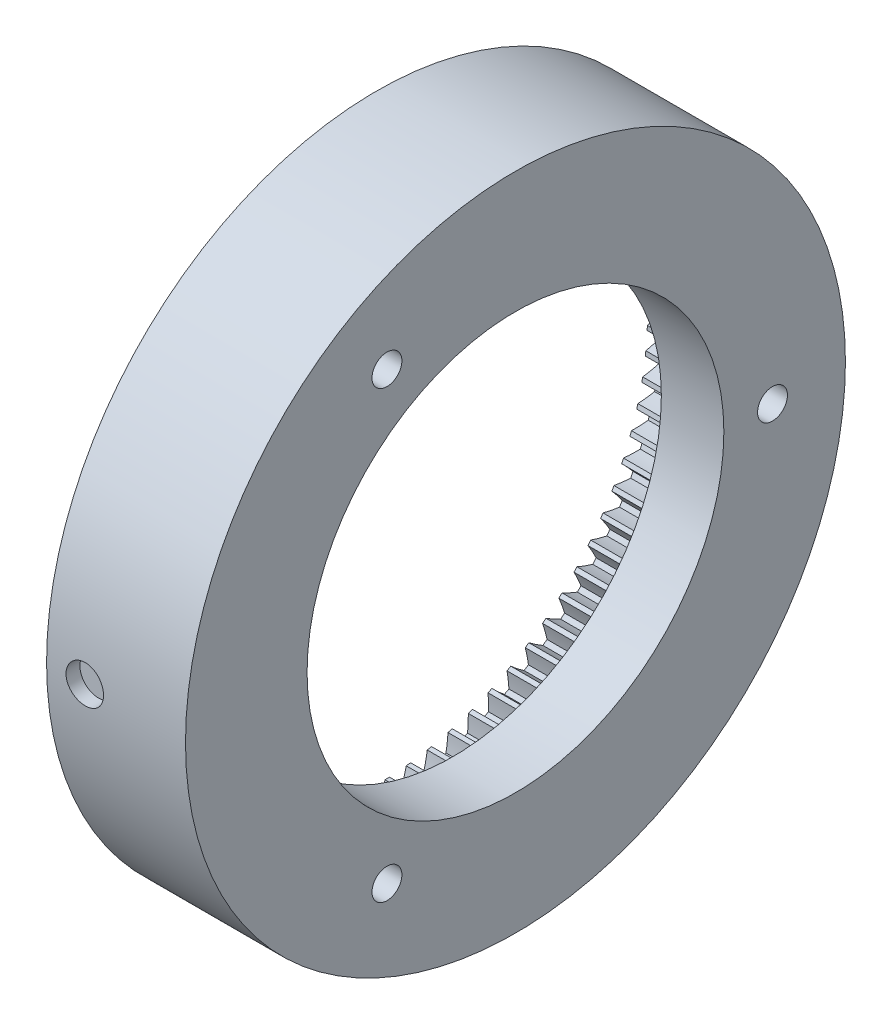
SolidWorks part; units mm, degrees
ref_plane "Plane1" through (0, 0, 0) normal (0, 0, 1) x (1, 0, 0)
ref_plane "Plane2" through (0, 0, 0) normal (0, 1, 0) x (1, 0, 0)
ref_plane "Plane3" through (0, 0, 0) normal (1, 0, 0) x (0, 0, -1)
other "Configuration Table"
sketch "HoldingSke" plane through (0, 0, 0) normal (0, 1, 0) x (1, 0, 0)
  line L0 (0, 0) -> (0.1736, -0.9848)
  line L1 (-15, 0) -> (100, 0) construction
  line L2 (0, 0) -> (-2.1039, 2.3779)
  line L3 (0, 0) -> (-11.863, 4.5341)
  line L4 (0, 0) -> (1.4996, 8.5048)
  line L5 (0, 0) -> (-23.7986, -8.8762)
  line L6 (0, 0) -> (-10.5278, -7.1032)
  line L7 (-2.1039, 2.3779) -> (3.3635, 27.1825)
  line L8 (-76.2, 3.3779) -> (-54.61, 3.3779)
  line L9 (-71.009, 38.7566) -> (-53.1078, 45.2721)
  line L10 (-76.2, 71.12) -> (104.1128, 71.12)
  line L11 (0, 0) -> (-10, 0)
  line L12 (-76.2, 101.6) -> (-76.162, 101.6)
  line L13 (24.9733, 27.94) -> (52.9518, 28.4284)
  line L14 (24.9733, 27.94) -> (24.9743, 27.94)
  line L15 (24.9733, 27.94) -> (100.4006, 29.5858)
  circle A0 centre (0, 0) radius 47.5
  circle A1 centre (0, 0) radius 12.7
  circle A2 centre (0, 0) radius 12.7
  dimension "Num_teeth" = 80
  dimension "Pitch_radius" = 180.3128
  dimension "Width" = 10
  dimension "Diameter" = 95
sketch "BasProSke" plane through (0, 0, 0) normal (0, 1, 0) x (1, 0, 0)
  line L0 (-10, 0) -> (60, 0) construction
  line L1 (0, 39) -> (0, 47.5)
  line L2 (0, 39) -> (10, 39)
  line L3 (10, 39) -> (10, 47.5)
  line L4 (10, 47.5) -> (0, 47.5)
  dimension "Thickness" = 10
  dimension "Diameter" = 95
revolve "Base-Revolve" add sketch "BasProSke" angle 360 about L0
sketch "TooCutSke" plane through (0, 0, 0) normal (1, 0, 0) x (0, 0, -1)
  line L3 (0.8803, 39.9903) -> (0.8803, 53.6633) construction
  line L4 (0, 0) -> (0, 59.563) construction
  line L5 (0, 0) -> (-2.6825, 68.2748) construction
  line L6 (-17.914, 33.1512) -> (36.4855, 35.2886) construction
  circle A0 centre (0, 0) radius 40 construction
  circle A1 centre (0, 0) radius 41.251 construction
  circle A2 centre (0, 0) radius 33.8289 construction
  circle A3 centre (0, 0) radius 38.9746 construction
  arc A4 (1.2253, 38.9553) -> (0.3732, 41.2493) centre (-17.914, 33.1512) ccw
  arc A5 (1.2253, 38.9553) -> (-1.2253, 38.9553) centre (0, 0) ccw
  arc A6 (0.3732, 41.2493) -> (-0.3732, 41.2493) centre (0, 0) ccw
  arc A7 (-0.3732, 41.2493) -> (-1.2253, 38.9553) centre (17.914, 33.1512) ccw
extrude "ToothCut" cut sketch "TooCutSke" along normal through all
fillet "Breaks" [suppressed] radius 0.1
fillet "RootFillets" [suppressed] radius 0.251
pattern_circular "TeethCuts" count 80 every 4.5 about axis through (-10, 0, 0) along (1, 0, 0) of "RootFillets", "Breaks", "ToothCut"
sketch "Sketch1" plane through (10, 0, 0) normal (1, 0, 0) x (0, 0, -1)
  circle A1 centre (0, 0) radius 47.5
  circle A2 centre (0, 0) radius 47.5
  arc A322 (2.8643, 41.1514) -> (1.8447, 38.9564) centre (20.4598, 31.6435) ccw
  arc A323 (3.6084, 41.0929) -> (2.8643, 41.1514) centre (0, 0) ccw
  arc A324 (4.2722, 38.7653) -> (3.6084, 41.0929) centre (-15.2577, 34.4545) ccw
  arc A325 (4.8955, 38.6915) -> (4.2722, 38.7653) centre (0, 0) ccw
  arc A326 (6.0842, 40.7998) -> (4.8955, 38.6915) centre (22.8794, 29.9407) ccw
  arc A327 (6.8214, 40.6831) -> (6.0842, 40.7998) centre (0, 0) ccw
  arc A328 (7.3005, 38.3106) -> (6.8214, 40.6831) centre (-12.5074, 35.5454) ccw
  arc A329 (7.9161, 38.1882) -> (7.3005, 38.3106) centre (0, 0) ccw
  arc A330 (9.2666, 40.1967) -> (7.9161, 38.1882) centre (25.158, 28.0533) ccw
  arc A331 (9.9923, 40.0225) -> (9.2666, 40.1967) centre (0, 0) ccw
  arc A332 (10.2838, 37.6197) -> (9.9923, 40.0225) centre (-9.68, 36.4172) ccw
  arc A333 (10.8879, 37.4494) -> (10.2838, 37.6197) centre (0, 0) ccw
  arc A334 (12.3918, 39.3458) -> (10.8879, 37.4494) centre (27.2815, 25.9929) ccw
  arc A335 (13.1017, 39.1151) -> (12.3918, 39.3458) centre (0, 0) ccw
  arc A336 (13.2037, 36.6969) -> (13.1017, 39.1151) centre (-6.7929, 37.0644) ccw
  arc A337 (13.7926, 36.4797) -> (13.2037, 36.6969) centre (0, 0) ccw
  arc A338 (15.4406, 38.2522) -> (13.7926, 36.4797) centre (29.2368, 23.7723) ccw
  arc A339 (16.1302, 37.9666) -> (15.4406, 38.2522) centre (0, 0) ccw
  arc A340 (16.0422, 35.5478) -> (16.1302, 37.9666) centre (-3.8639, 37.4831) ccw
  arc A341 (16.6122, 35.2851) -> (16.0422, 35.5478) centre (0, 0) ccw
  arc A342 (18.3943, 36.9228) -> (16.6122, 35.2851) centre (31.0118, 21.4052) ccw
  arc A343 (19.0593, 36.584) -> (18.3943, 36.9228) centre (0, 0) ccw
  arc A344 (18.7818, 34.1796) -> (19.0593, 36.584) centre (-0.9111, 37.6707) ccw
  arc A345 (19.3294, 33.8729) -> (18.7818, 34.1796) centre (0, 0) ccw
  arc A346 (21.2345, 35.3658) -> (19.3294, 33.8729) centre (32.5956, 18.906) ccw
  arc A347 (21.8709, 34.9758) -> (21.2345, 35.3658) centre (0, 0) ccw
  arc A348 (21.4056, 32.6006) -> (21.8709, 34.9758) centre (2.0473, 37.6261) ccw
  arc A349 (21.9275, 32.2519) -> (21.4056, 32.6006) centre (0, 0) ccw
  arc A350 (23.9438, 33.5908) -> (21.9275, 32.2519) centre (33.9785, 16.2903) ccw
  arc A351 (24.5477, 33.152) -> (23.9438, 33.5908) centre (0, 0) ccw
  arc A352 (23.8974, 30.8207) -> (24.5477, 33.152) centre (4.9931, 37.3494) ccw
  arc A353 (24.3903, 30.4321) -> (23.8974, 30.8207) centre (0, 0) ccw
  arc A354 (26.5055, 31.6086) -> (24.3903, 30.4321) centre (35.1519, 13.5742) ccw
  arc A355 (27.0731, 31.1239) -> (26.5055, 31.6086) centre (0, 0) ccw
  arc A356 (26.2419, 28.8507) -> (27.0731, 31.1239) centre (7.9081, 36.8426) ccw
  arc A357 (26.7028, 28.4246) -> (26.2419, 28.8507) centre (0, 0) ccw
  arc A358 (28.9038, 29.4316) -> (26.7028, 28.4246) centre (36.1085, 10.7743) ccw
  arc A359 (29.4316, 28.9038) -> (28.9038, 29.4316) centre (0, 0) ccw
  arc A360 (28.4246, 26.7028) -> (29.4316, 28.9038) centre (10.7743, 36.1085) ccw
  arc A361 (28.8507, 26.2419) -> (28.4246, 26.7028) centre (0, 0) ccw
  arc A362 (31.1239, 27.0731) -> (28.8507, 26.2419) centre (36.8426, 7.9081) ccw
  arc A363 (31.6086, 26.5055) -> (31.1239, 27.0731) centre (0, 0) ccw
  arc A364 (30.4321, 24.3903) -> (31.6086, 26.5055) centre (13.5742, 35.1519) ccw
  arc A365 (30.8207, 23.8974) -> (30.4321, 24.3903) centre (0, 0) ccw
  arc A366 (33.152, 24.5477) -> (30.8207, 23.8974) centre (37.3494, 4.9931) ccw
  arc A367 (33.5908, 23.9438) -> (33.152, 24.5477) centre (0, 0) ccw
  arc A368 (32.2519, 21.9275) -> (33.5908, 23.9438) centre (16.2903, 33.9785) ccw
  arc A369 (32.6006, 21.4056) -> (32.2519, 21.9275) centre (0, 0) ccw
  arc A370 (34.9758, 21.8709) -> (32.6006, 21.4056) centre (37.6261, 2.0473) ccw
  arc A371 (35.3658, 21.2345) -> (34.9758, 21.8709) centre (0, 0) ccw
  arc A372 (33.8729, 19.3294) -> (35.3658, 21.2345) centre (18.906, 32.5956) ccw
  arc A373 (34.1796, 18.7818) -> (33.8729, 19.3294) centre (0, 0) ccw
  arc A374 (36.584, 19.0593) -> (34.1796, 18.7818) centre (37.6707, -0.9111) ccw
  arc A375 (36.9228, 18.3943) -> (36.584, 19.0593) centre (0, 0) ccw
  arc A376 (35.2851, 16.6122) -> (36.9228, 18.3943) centre (21.4052, 31.0118) ccw
  arc A377 (35.5478, 16.0422) -> (35.2851, 16.6122) centre (0, 0) ccw
  arc A378 (37.9666, 16.1302) -> (35.5478, 16.0422) centre (37.4831, -3.8639) ccw
  arc A379 (38.2522, 15.4406) -> (37.9666, 16.1302) centre (0, 0) ccw
  arc A380 (36.4797, 13.7926) -> (38.2522, 15.4406) centre (23.7723, 29.2368) ccw
  arc A381 (36.6969, 13.2037) -> (36.4797, 13.7926) centre (0, 0) ccw
  arc A382 (39.1151, 13.1017) -> (36.6969, 13.2037) centre (37.0644, -6.7929) ccw
  arc A383 (39.3458, 12.3918) -> (39.1151, 13.1017) centre (0, 0) ccw
  arc A384 (37.4494, 10.8879) -> (39.3458, 12.3918) centre (25.9929, 27.2815) ccw
  arc A385 (37.6197, 10.2838) -> (37.4494, 10.8879) centre (0, 0) ccw
  arc A386 (40.0225, 9.9923) -> (37.6197, 10.2838) centre (36.4172, -9.68) ccw
  arc A387 (40.1967, 9.2666) -> (40.0225, 9.9923) centre (0, 0) ccw
  arc A388 (38.1882, 7.9161) -> (40.1967, 9.2666) centre (28.0533, 25.158) ccw
  arc A389 (38.3106, 7.3005) -> (38.1882, 7.9161) centre (0, 0) ccw
  arc A390 (40.6831, 6.8214) -> (38.3106, 7.3005) centre (35.5454, -12.5074) ccw
  arc A391 (40.7998, 6.0842) -> (40.6831, 6.8214) centre (0, 0) ccw
  arc A392 (38.6915, 4.8955) -> (40.7998, 6.0842) centre (29.9407, 22.8794) ccw
  arc A393 (38.7653, 4.2722) -> (38.6915, 4.8955) centre (0, 0) ccw
  arc A394 (41.0929, 3.6084) -> (38.7653, 4.2722) centre (34.4545, -15.2577) ccw
  arc A395 (41.1514, 2.8643) -> (41.0929, 3.6084) centre (0, 0) ccw
  arc A396 (38.9564, 1.8447) -> (41.1514, 2.8643) centre (31.6435, 20.4598) ccw
  arc A397 (38.981, 1.2175) -> (38.9564, 1.8447) centre (0, 0) ccw
  arc A398 (41.2493, 0.3732) -> (38.981, 1.2175) centre (33.1512, -17.914) ccw
  arc A399 (41.2493, -0.3732) -> (41.2493, 0.3732) centre (0, 0) ccw
  arc A400 (38.981, -1.2175) -> (41.2493, -0.3732) centre (33.1512, 17.914) ccw
  arc A401 (38.9564, -1.8447) -> (38.981, -1.2175) centre (0, 0) ccw
  arc A402 (41.1514, -2.8643) -> (38.9564, -1.8447) centre (31.6435, -20.4598) ccw
  arc A403 (41.0929, -3.6084) -> (41.1514, -2.8643) centre (0, 0) ccw
  arc A404 (38.7653, -4.2722) -> (41.0929, -3.6084) centre (34.4545, 15.2577) ccw
  arc A405 (38.6915, -4.8955) -> (38.7653, -4.2722) centre (0, 0) ccw
  arc A406 (40.7998, -6.0842) -> (38.6915, -4.8955) centre (29.9407, -22.8794) ccw
  arc A407 (40.6831, -6.8214) -> (40.7998, -6.0842) centre (0, 0) ccw
  arc A408 (38.3106, -7.3005) -> (40.6831, -6.8214) centre (35.5454, 12.5074) ccw
  arc A409 (38.1882, -7.9161) -> (38.3106, -7.3005) centre (0, 0) ccw
  arc A410 (40.1967, -9.2666) -> (38.1882, -7.9161) centre (28.0533, -25.158) ccw
  arc A411 (40.0225, -9.9923) -> (40.1967, -9.2666) centre (0, 0) ccw
  arc A412 (37.6197, -10.2838) -> (40.0225, -9.9923) centre (36.4172, 9.68) ccw
  arc A413 (37.4494, -10.8879) -> (37.6197, -10.2838) centre (0, 0) ccw
  arc A414 (39.3458, -12.3918) -> (37.4494, -10.8879) centre (25.9929, -27.2815) ccw
  arc A415 (39.1151, -13.1017) -> (39.3458, -12.3918) centre (0, 0) ccw
  arc A416 (36.6969, -13.2037) -> (39.1151, -13.1017) centre (37.0644, 6.7929) ccw
  arc A417 (36.4797, -13.7926) -> (36.6969, -13.2037) centre (0, 0) ccw
  arc A418 (38.2522, -15.4406) -> (36.4797, -13.7926) centre (23.7723, -29.2368) ccw
  arc A419 (37.9666, -16.1302) -> (38.2522, -15.4406) centre (0, 0) ccw
  arc A420 (35.5478, -16.0422) -> (37.9666, -16.1302) centre (37.4831, 3.8639) ccw
  arc A421 (35.2851, -16.6122) -> (35.5478, -16.0422) centre (0, 0) ccw
  arc A422 (36.9228, -18.3943) -> (35.2851, -16.6122) centre (21.4052, -31.0118) ccw
  arc A423 (36.584, -19.0593) -> (36.9228, -18.3943) centre (0, 0) ccw
  arc A424 (34.1796, -18.7818) -> (36.584, -19.0593) centre (37.6707, 0.9111) ccw
  arc A425 (33.8729, -19.3294) -> (34.1796, -18.7818) centre (0, 0) ccw
  arc A426 (35.3658, -21.2345) -> (33.8729, -19.3294) centre (18.906, -32.5956) ccw
  arc A427 (34.9758, -21.8709) -> (35.3658, -21.2345) centre (0, 0) ccw
  arc A428 (32.6006, -21.4056) -> (34.9758, -21.8709) centre (37.6261, -2.0473) ccw
  arc A429 (32.2519, -21.9275) -> (32.6006, -21.4056) centre (0, 0) ccw
  arc A430 (33.5908, -23.9438) -> (32.2519, -21.9275) centre (16.2903, -33.9785) ccw
  arc A431 (33.152, -24.5477) -> (33.5908, -23.9438) centre (0, 0) ccw
  arc A432 (30.8207, -23.8974) -> (33.152, -24.5477) centre (37.3494, -4.9931) ccw
  arc A433 (30.4321, -24.3903) -> (30.8207, -23.8974) centre (0, 0) ccw
  arc A434 (31.6086, -26.5055) -> (30.4321, -24.3903) centre (13.5742, -35.1519) ccw
  arc A435 (31.1239, -27.0731) -> (31.6086, -26.5055) centre (0, 0) ccw
  arc A436 (28.8507, -26.2419) -> (31.1239, -27.0731) centre (36.8426, -7.9081) ccw
  arc A437 (28.4246, -26.7028) -> (28.8507, -26.2419) centre (0, 0) ccw
  arc A438 (29.4316, -28.9038) -> (28.4246, -26.7028) centre (10.7743, -36.1085) ccw
  arc A439 (28.9038, -29.4316) -> (29.4316, -28.9038) centre (0, 0) ccw
  arc A440 (26.7028, -28.4246) -> (28.9038, -29.4316) centre (36.1085, -10.7743) ccw
  arc A441 (26.2419, -28.8507) -> (26.7028, -28.4246) centre (0, 0) ccw
  arc A442 (27.0731, -31.1239) -> (26.2419, -28.8507) centre (7.9081, -36.8426) ccw
  arc A443 (26.5055, -31.6086) -> (27.0731, -31.1239) centre (0, 0) ccw
  arc A444 (24.3903, -30.4321) -> (26.5055, -31.6086) centre (35.1519, -13.5742) ccw
  arc A445 (23.8974, -30.8207) -> (24.3903, -30.4321) centre (0, 0) ccw
  arc A446 (24.5477, -33.152) -> (23.8974, -30.8207) centre (4.9931, -37.3494) ccw
  arc A447 (23.9438, -33.5908) -> (24.5477, -33.152) centre (0, 0) ccw
  arc A448 (21.9275, -32.2519) -> (23.9438, -33.5908) centre (33.9785, -16.2903) ccw
  arc A449 (21.4056, -32.6006) -> (21.9275, -32.2519) centre (0, 0) ccw
  arc A450 (21.8709, -34.9758) -> (21.4056, -32.6006) centre (2.0473, -37.6261) ccw
  arc A451 (21.2345, -35.3658) -> (21.8709, -34.9758) centre (0, 0) ccw
  arc A452 (19.3294, -33.8729) -> (21.2345, -35.3658) centre (32.5956, -18.906) ccw
  arc A453 (18.7818, -34.1796) -> (19.3294, -33.8729) centre (0, 0) ccw
  arc A454 (19.0593, -36.584) -> (18.7818, -34.1796) centre (-0.9111, -37.6707) ccw
  arc A455 (18.3943, -36.9228) -> (19.0593, -36.584) centre (0, 0) ccw
  arc A456 (16.6122, -35.2851) -> (18.3943, -36.9228) centre (31.0118, -21.4052) ccw
  arc A457 (16.0422, -35.5478) -> (16.6122, -35.2851) centre (0, 0) ccw
  arc A458 (16.1302, -37.9666) -> (16.0422, -35.5478) centre (-3.8639, -37.4831) ccw
  arc A459 (15.4406, -38.2522) -> (16.1302, -37.9666) centre (0, 0) ccw
  arc A460 (13.7926, -36.4797) -> (15.4406, -38.2522) centre (29.2368, -23.7723) ccw
  arc A461 (13.2037, -36.6969) -> (13.7926, -36.4797) centre (0, 0) ccw
  arc A462 (13.1017, -39.1151) -> (13.2037, -36.6969) centre (-6.7929, -37.0644) ccw
  arc A463 (12.3918, -39.3458) -> (13.1017, -39.1151) centre (0, 0) ccw
  arc A464 (10.8879, -37.4494) -> (12.3918, -39.3458) centre (27.2815, -25.9929) ccw
  arc A465 (10.2838, -37.6197) -> (10.8879, -37.4494) centre (0, 0) ccw
  arc A466 (9.9923, -40.0225) -> (10.2838, -37.6197) centre (-9.68, -36.4172) ccw
  arc A467 (9.2666, -40.1967) -> (9.9923, -40.0225) centre (0, 0) ccw
  arc A468 (7.9161, -38.1882) -> (9.2666, -40.1967) centre (25.158, -28.0533) ccw
  arc A469 (7.3005, -38.3106) -> (7.9161, -38.1882) centre (0, 0) ccw
  arc A470 (6.8214, -40.6831) -> (7.3005, -38.3106) centre (-12.5074, -35.5454) ccw
  arc A471 (6.0842, -40.7998) -> (6.8214, -40.6831) centre (0, 0) ccw
  arc A472 (4.8955, -38.6915) -> (6.0842, -40.7998) centre (22.8794, -29.9407) ccw
  arc A473 (4.2722, -38.7653) -> (4.8955, -38.6915) centre (0, 0) ccw
  arc A474 (3.6084, -41.0929) -> (4.2722, -38.7653) centre (-15.2577, -34.4545) ccw
  arc A475 (2.8643, -41.1514) -> (3.6084, -41.0929) centre (0, 0) ccw
  arc A476 (1.8447, -38.9564) -> (2.8643, -41.1514) centre (20.4598, -31.6435) ccw
  arc A477 (1.2175, -38.981) -> (1.8447, -38.9564) centre (0, 0) ccw
  arc A478 (0.3732, -41.2493) -> (1.2175, -38.981) centre (-17.914, -33.1512) ccw
  arc A479 (-0.3732, -41.2493) -> (0.3732, -41.2493) centre (0, 0) ccw
  arc A480 (-1.2175, -38.981) -> (-0.3732, -41.2493) centre (17.914, -33.1512) ccw
  arc A481 (-1.8447, -38.9564) -> (-1.2175, -38.981) centre (0, 0) ccw
  arc A482 (-2.8643, -41.1514) -> (-1.8447, -38.9564) centre (-20.4598, -31.6435) ccw
  arc A483 (-3.6084, -41.0929) -> (-2.8643, -41.1514) centre (0, 0) ccw
  arc A484 (-4.2722, -38.7653) -> (-3.6084, -41.0929) centre (15.2577, -34.4545) ccw
  arc A485 (-4.8955, -38.6915) -> (-4.2722, -38.7653) centre (0, 0) ccw
  arc A486 (-6.0842, -40.7998) -> (-4.8955, -38.6915) centre (-22.8794, -29.9407) ccw
  arc A487 (-6.8214, -40.6831) -> (-6.0842, -40.7998) centre (0, 0) ccw
  arc A488 (-7.3005, -38.3106) -> (-6.8214, -40.6831) centre (12.5074, -35.5454) ccw
  arc A489 (-7.9161, -38.1882) -> (-7.3005, -38.3106) centre (0, 0) ccw
  arc A490 (-9.2666, -40.1967) -> (-7.9161, -38.1882) centre (-25.158, -28.0533) ccw
  arc A491 (-9.9923, -40.0225) -> (-9.2666, -40.1967) centre (0, 0) ccw
  arc A492 (-10.2838, -37.6197) -> (-9.9923, -40.0225) centre (9.68, -36.4172) ccw
  arc A493 (-10.8879, -37.4494) -> (-10.2838, -37.6197) centre (0, 0) ccw
  arc A494 (-12.3918, -39.3458) -> (-10.8879, -37.4494) centre (-27.2815, -25.9929) ccw
  arc A495 (-13.1017, -39.1151) -> (-12.3918, -39.3458) centre (0, 0) ccw
  arc A496 (-13.2037, -36.6969) -> (-13.1017, -39.1151) centre (6.7929, -37.0644) ccw
  arc A497 (-13.7926, -36.4797) -> (-13.2037, -36.6969) centre (0, 0) ccw
  arc A498 (-15.4406, -38.2522) -> (-13.7926, -36.4797) centre (-29.2368, -23.7723) ccw
  arc A499 (-16.1302, -37.9666) -> (-15.4406, -38.2522) centre (0, 0) ccw
  arc A500 (-16.0422, -35.5478) -> (-16.1302, -37.9666) centre (3.8639, -37.4831) ccw
  arc A501 (-16.6122, -35.2851) -> (-16.0422, -35.5478) centre (0, 0) ccw
  arc A502 (-18.3943, -36.9228) -> (-16.6122, -35.2851) centre (-31.0118, -21.4052) ccw
  arc A503 (-19.0593, -36.584) -> (-18.3943, -36.9228) centre (0, 0) ccw
  arc A504 (-18.7818, -34.1796) -> (-19.0593, -36.584) centre (0.9111, -37.6707) ccw
  arc A505 (-19.3294, -33.8729) -> (-18.7818, -34.1796) centre (0, 0) ccw
  arc A506 (-21.2345, -35.3658) -> (-19.3294, -33.8729) centre (-32.5956, -18.906) ccw
  arc A507 (-21.8709, -34.9758) -> (-21.2345, -35.3658) centre (0, 0) ccw
  arc A508 (-21.4056, -32.6006) -> (-21.8709, -34.9758) centre (-2.0473, -37.6261) ccw
  arc A509 (-21.9275, -32.2519) -> (-21.4056, -32.6006) centre (0, 0) ccw
  arc A510 (-23.9438, -33.5908) -> (-21.9275, -32.2519) centre (-33.9785, -16.2903) ccw
  arc A511 (-24.5477, -33.152) -> (-23.9438, -33.5908) centre (0, 0) ccw
  arc A512 (-23.8974, -30.8207) -> (-24.5477, -33.152) centre (-4.9931, -37.3494) ccw
  arc A513 (-24.3903, -30.4321) -> (-23.8974, -30.8207) centre (0, 0) ccw
  arc A514 (-26.5055, -31.6086) -> (-24.3903, -30.4321) centre (-35.1519, -13.5742) ccw
  arc A515 (-27.0731, -31.1239) -> (-26.5055, -31.6086) centre (0, 0) ccw
  arc A516 (-26.2419, -28.8507) -> (-27.0731, -31.1239) centre (-7.9081, -36.8426) ccw
  arc A517 (-26.7028, -28.4246) -> (-26.2419, -28.8507) centre (0, 0) ccw
  arc A518 (-28.9038, -29.4316) -> (-26.7028, -28.4246) centre (-36.1085, -10.7743) ccw
  arc A519 (-29.4316, -28.9038) -> (-28.9038, -29.4316) centre (0, 0) ccw
  arc A520 (-28.4246, -26.7028) -> (-29.4316, -28.9038) centre (-10.7743, -36.1085) ccw
  arc A521 (-28.8507, -26.2419) -> (-28.4246, -26.7028) centre (0, 0) ccw
  arc A522 (-31.1239, -27.0731) -> (-28.8507, -26.2419) centre (-36.8426, -7.9081) ccw
  arc A523 (-31.6086, -26.5055) -> (-31.1239, -27.0731) centre (0, 0) ccw
  arc A524 (-30.4321, -24.3903) -> (-31.6086, -26.5055) centre (-13.5742, -35.1519) ccw
  arc A525 (-30.8207, -23.8974) -> (-30.4321, -24.3903) centre (0, 0) ccw
  arc A526 (-33.152, -24.5477) -> (-30.8207, -23.8974) centre (-37.3494, -4.9931) ccw
  arc A527 (-33.5908, -23.9438) -> (-33.152, -24.5477) centre (0, 0) ccw
  arc A528 (-32.2519, -21.9275) -> (-33.5908, -23.9438) centre (-16.2903, -33.9785) ccw
  arc A529 (-32.6006, -21.4056) -> (-32.2519, -21.9275) centre (0, 0) ccw
  arc A530 (-34.9758, -21.8709) -> (-32.6006, -21.4056) centre (-37.6261, -2.0473) ccw
  arc A531 (-35.3658, -21.2345) -> (-34.9758, -21.8709) centre (0, 0) ccw
  arc A532 (-33.8729, -19.3294) -> (-35.3658, -21.2345) centre (-18.906, -32.5956) ccw
  arc A533 (-34.1796, -18.7818) -> (-33.8729, -19.3294) centre (0, 0) ccw
  arc A534 (-36.584, -19.0593) -> (-34.1796, -18.7818) centre (-37.6707, 0.9111) ccw
  arc A535 (-36.9228, -18.3943) -> (-36.584, -19.0593) centre (0, 0) ccw
  arc A536 (-35.2851, -16.6122) -> (-36.9228, -18.3943) centre (-21.4052, -31.0118) ccw
  arc A537 (-35.5478, -16.0422) -> (-35.2851, -16.6122) centre (0, 0) ccw
  arc A538 (-37.9666, -16.1302) -> (-35.5478, -16.0422) centre (-37.4831, 3.8639) ccw
  arc A539 (-38.2522, -15.4406) -> (-37.9666, -16.1302) centre (0, 0) ccw
  arc A540 (-36.4797, -13.7926) -> (-38.2522, -15.4406) centre (-23.7723, -29.2368) ccw
  arc A541 (-36.6969, -13.2037) -> (-36.4797, -13.7926) centre (0, 0) ccw
  arc A542 (-39.1151, -13.1017) -> (-36.6969, -13.2037) centre (-37.0644, 6.7929) ccw
  arc A543 (-39.3458, -12.3918) -> (-39.1151, -13.1017) centre (0, 0) ccw
  arc A544 (-37.4494, -10.8879) -> (-39.3458, -12.3918) centre (-25.9929, -27.2815) ccw
  arc A545 (-37.6197, -10.2838) -> (-37.4494, -10.8879) centre (0, 0) ccw
  arc A546 (-40.0225, -9.9923) -> (-37.6197, -10.2838) centre (-36.4172, 9.68) ccw
  arc A547 (-40.1967, -9.2666) -> (-40.0225, -9.9923) centre (0, 0) ccw
  arc A548 (-38.1882, -7.9161) -> (-40.1967, -9.2666) centre (-28.0533, -25.158) ccw
  arc A549 (-38.3106, -7.3005) -> (-38.1882, -7.9161) centre (0, 0) ccw
  arc A550 (-40.6831, -6.8214) -> (-38.3106, -7.3005) centre (-35.5454, 12.5074) ccw
  arc A551 (-40.7998, -6.0842) -> (-40.6831, -6.8214) centre (0, 0) ccw
  arc A552 (-38.6915, -4.8955) -> (-40.7998, -6.0842) centre (-29.9407, -22.8794) ccw
  arc A553 (-38.7653, -4.2722) -> (-38.6915, -4.8955) centre (0, 0) ccw
  arc A554 (-41.0929, -3.6084) -> (-38.7653, -4.2722) centre (-34.4545, 15.2577) ccw
  arc A555 (-41.1514, -2.8643) -> (-41.0929, -3.6084) centre (0, 0) ccw
  arc A556 (-38.9564, -1.8447) -> (-41.1514, -2.8643) centre (-31.6435, -20.4598) ccw
  arc A557 (-38.981, -1.2175) -> (-38.9564, -1.8447) centre (0, 0) ccw
  arc A558 (-41.2493, -0.3732) -> (-38.981, -1.2175) centre (-33.1512, 17.914) ccw
  arc A559 (-41.2493, 0.3732) -> (-41.2493, -0.3732) centre (0, 0) ccw
  arc A560 (-38.981, 1.2175) -> (-41.2493, 0.3732) centre (-33.1512, -17.914) ccw
  arc A561 (-38.9564, 1.8447) -> (-38.981, 1.2175) centre (0, 0) ccw
  arc A562 (-41.1514, 2.8643) -> (-38.9564, 1.8447) centre (-31.6435, 20.4598) ccw
  arc A563 (-41.0929, 3.6084) -> (-41.1514, 2.8643) centre (0, 0) ccw
  arc A564 (-38.7653, 4.2722) -> (-41.0929, 3.6084) centre (-34.4545, -15.2577) ccw
  arc A565 (-38.6915, 4.8955) -> (-38.7653, 4.2722) centre (0, 0) ccw
  arc A566 (-40.7998, 6.0842) -> (-38.6915, 4.8955) centre (-29.9407, 22.8794) ccw
  arc A567 (-40.6831, 6.8214) -> (-40.7998, 6.0842) centre (0, 0) ccw
  arc A568 (-38.3106, 7.3005) -> (-40.6831, 6.8214) centre (-35.5454, -12.5074) ccw
  arc A569 (-38.1882, 7.9161) -> (-38.3106, 7.3005) centre (0, 0) ccw
  arc A570 (-40.1967, 9.2666) -> (-38.1882, 7.9161) centre (-28.0533, 25.158) ccw
  arc A571 (-40.0225, 9.9923) -> (-40.1967, 9.2666) centre (0, 0) ccw
  arc A572 (-37.6197, 10.2838) -> (-40.0225, 9.9923) centre (-36.4172, -9.68) ccw
  arc A573 (-37.4494, 10.8879) -> (-37.6197, 10.2838) centre (0, 0) ccw
  arc A574 (-39.3458, 12.3918) -> (-37.4494, 10.8879) centre (-25.9929, 27.2815) ccw
  arc A575 (-39.1151, 13.1017) -> (-39.3458, 12.3918) centre (0, 0) ccw
  arc A576 (-36.6969, 13.2037) -> (-39.1151, 13.1017) centre (-37.0644, -6.7929) ccw
  arc A577 (-36.4797, 13.7926) -> (-36.6969, 13.2037) centre (0, 0) ccw
  arc A578 (-38.2522, 15.4406) -> (-36.4797, 13.7926) centre (-23.7723, 29.2368) ccw
  arc A579 (-37.9666, 16.1302) -> (-38.2522, 15.4406) centre (0, 0) ccw
  arc A580 (-35.5478, 16.0422) -> (-37.9666, 16.1302) centre (-37.4831, -3.8639) ccw
  arc A581 (-35.2851, 16.6122) -> (-35.5478, 16.0422) centre (0, 0) ccw
  arc A582 (-36.9228, 18.3943) -> (-35.2851, 16.6122) centre (-21.4052, 31.0118) ccw
  arc A583 (-36.584, 19.0593) -> (-36.9228, 18.3943) centre (0, 0) ccw
  arc A584 (-34.1796, 18.7818) -> (-36.584, 19.0593) centre (-37.6707, -0.9111) ccw
  arc A585 (-33.8729, 19.3294) -> (-34.1796, 18.7818) centre (0, 0) ccw
  arc A586 (-35.3658, 21.2345) -> (-33.8729, 19.3294) centre (-18.906, 32.5956) ccw
  arc A587 (-34.9758, 21.8709) -> (-35.3658, 21.2345) centre (0, 0) ccw
  arc A588 (-32.6006, 21.4056) -> (-34.9758, 21.8709) centre (-37.6261, 2.0473) ccw
  arc A589 (-32.2519, 21.9275) -> (-32.6006, 21.4056) centre (0, 0) ccw
  arc A590 (-33.5908, 23.9438) -> (-32.2519, 21.9275) centre (-16.2903, 33.9785) ccw
  arc A591 (-33.152, 24.5477) -> (-33.5908, 23.9438) centre (0, 0) ccw
  arc A592 (-30.8207, 23.8974) -> (-33.152, 24.5477) centre (-37.3494, 4.9931) ccw
  arc A593 (-30.4321, 24.3903) -> (-30.8207, 23.8974) centre (0, 0) ccw
  arc A594 (-31.6086, 26.5055) -> (-30.4321, 24.3903) centre (-13.5742, 35.1519) ccw
  arc A595 (-31.1239, 27.0731) -> (-31.6086, 26.5055) centre (0, 0) ccw
  arc A596 (-28.8507, 26.2419) -> (-31.1239, 27.0731) centre (-36.8426, 7.9081) ccw
  arc A597 (-28.4246, 26.7028) -> (-28.8507, 26.2419) centre (0, 0) ccw
  arc A598 (-29.4316, 28.9038) -> (-28.4246, 26.7028) centre (-10.7743, 36.1085) ccw
  arc A599 (-28.9038, 29.4316) -> (-29.4316, 28.9038) centre (0, 0) ccw
  arc A600 (-26.7028, 28.4246) -> (-28.9038, 29.4316) centre (-36.1085, 10.7743) ccw
  arc A601 (-26.2419, 28.8507) -> (-26.7028, 28.4246) centre (0, 0) ccw
  arc A602 (-27.0731, 31.1239) -> (-26.2419, 28.8507) centre (-7.9081, 36.8426) ccw
  arc A603 (-26.5055, 31.6086) -> (-27.0731, 31.1239) centre (0, 0) ccw
  arc A604 (-24.3903, 30.4321) -> (-26.5055, 31.6086) centre (-35.1519, 13.5742) ccw
  arc A605 (-23.8974, 30.8207) -> (-24.3903, 30.4321) centre (0, 0) ccw
  arc A606 (-24.5477, 33.152) -> (-23.8974, 30.8207) centre (-4.9931, 37.3494) ccw
  arc A607 (-23.9438, 33.5908) -> (-24.5477, 33.152) centre (0, 0) ccw
  arc A608 (-21.9275, 32.2519) -> (-23.9438, 33.5908) centre (-33.9785, 16.2903) ccw
  arc A609 (-21.4056, 32.6006) -> (-21.9275, 32.2519) centre (0, 0) ccw
  arc A610 (-21.8709, 34.9758) -> (-21.4056, 32.6006) centre (-2.0473, 37.6261) ccw
  arc A611 (-21.2345, 35.3658) -> (-21.8709, 34.9758) centre (0, 0) ccw
  arc A612 (-19.3294, 33.8729) -> (-21.2345, 35.3658) centre (-32.5956, 18.906) ccw
  arc A613 (-18.7818, 34.1796) -> (-19.3294, 33.8729) centre (0, 0) ccw
  arc A614 (-19.0593, 36.584) -> (-18.7818, 34.1796) centre (0.9111, 37.6707) ccw
  arc A615 (-18.3943, 36.9228) -> (-19.0593, 36.584) centre (0, 0) ccw
  arc A616 (-16.6122, 35.2851) -> (-18.3943, 36.9228) centre (-31.0118, 21.4052) ccw
  arc A617 (-16.0422, 35.5478) -> (-16.6122, 35.2851) centre (0, 0) ccw
  arc A618 (-16.1302, 37.9666) -> (-16.0422, 35.5478) centre (3.8639, 37.4831) ccw
  arc A619 (-15.4406, 38.2522) -> (-16.1302, 37.9666) centre (0, 0) ccw
  arc A620 (-13.7926, 36.4797) -> (-15.4406, 38.2522) centre (-29.2368, 23.7723) ccw
  arc A621 (-13.2037, 36.6969) -> (-13.7926, 36.4797) centre (0, 0) ccw
  arc A622 (-13.1017, 39.1151) -> (-13.2037, 36.6969) centre (6.7929, 37.0644) ccw
  arc A623 (-12.3918, 39.3458) -> (-13.1017, 39.1151) centre (0, 0) ccw
  arc A624 (-10.8879, 37.4494) -> (-12.3918, 39.3458) centre (-27.2815, 25.9929) ccw
  arc A625 (-10.2838, 37.6197) -> (-10.8879, 37.4494) centre (0, 0) ccw
  arc A626 (-9.9923, 40.0225) -> (-10.2838, 37.6197) centre (9.68, 36.4172) ccw
  arc A627 (-9.2666, 40.1967) -> (-9.9923, 40.0225) centre (0, 0) ccw
  arc A628 (-7.9161, 38.1882) -> (-9.2666, 40.1967) centre (-25.158, 28.0533) ccw
  arc A629 (-7.3005, 38.3106) -> (-7.9161, 38.1882) centre (0, 0) ccw
  arc A630 (-6.8214, 40.6831) -> (-7.3005, 38.3106) centre (12.5074, 35.5454) ccw
  arc A631 (-6.0842, 40.7998) -> (-6.8214, 40.6831) centre (0, 0) ccw
  arc A632 (-4.8955, 38.6915) -> (-6.0842, 40.7998) centre (-22.8794, 29.9407) ccw
  arc A633 (-4.2722, 38.7653) -> (-4.8955, 38.6915) centre (0, 0) ccw
  arc A634 (-3.6084, 41.0929) -> (-4.2722, 38.7653) centre (15.2577, 34.4545) ccw
  arc A635 (-2.8643, 41.1514) -> (-3.6084, 41.0929) centre (0, 0) ccw
  arc A636 (-1.8447, 38.9564) -> (-2.8643, 41.1514) centre (-20.4598, 31.6435) ccw
  arc A637 (-1.2175, 38.981) -> (-1.8447, 38.9564) centre (0, 0) ccw
  arc A638 (-0.3732, 41.2493) -> (-1.2175, 38.981) centre (17.914, 33.1512) ccw
  arc A639 (0.3732, 41.2493) -> (-0.3732, 41.2493) centre (0, 0) ccw
  arc A640 (1.2175, 38.981) -> (0.3732, 41.2493) centre (-17.914, 33.1512) ccw
  arc A641 (1.8447, 38.9564) -> (1.2175, 38.981) centre (0, 0) ccw
  arc A642 (2.8643, 41.1514) -> (1.8447, 38.9564) centre (20.4598, 31.6435) ccw
  arc A643 (3.6084, 41.0929) -> (2.8643, 41.1514) centre (0, 0) ccw
  arc A644 (4.2722, 38.7653) -> (3.6084, 41.0929) centre (-15.2577, 34.4545) ccw
  arc A645 (4.8955, 38.6915) -> (4.2722, 38.7653) centre (0, 0) ccw
  arc A646 (6.0842, 40.7998) -> (4.8955, 38.6915) centre (22.8794, 29.9407) ccw
  arc A647 (6.8214, 40.6831) -> (6.0842, 40.7998) centre (0, 0) ccw
  arc A648 (7.3005, 38.3106) -> (6.8214, 40.6831) centre (-12.5074, 35.5454) ccw
  arc A649 (7.9161, 38.1882) -> (7.3005, 38.3106) centre (0, 0) ccw
  arc A650 (9.2666, 40.1967) -> (7.9161, 38.1882) centre (25.158, 28.0533) ccw
  arc A651 (9.9923, 40.0225) -> (9.2666, 40.1967) centre (0, 0) ccw
  arc A652 (10.2838, 37.6197) -> (9.9923, 40.0225) centre (-9.68, 36.4172) ccw
  arc A653 (10.8879, 37.4494) -> (10.2838, 37.6197) centre (0, 0) ccw
  arc A654 (12.3918, 39.3458) -> (10.8879, 37.4494) centre (27.2815, 25.9929) ccw
  arc A655 (13.1017, 39.1151) -> (12.3918, 39.3458) centre (0, 0) ccw
  arc A656 (13.2037, 36.6969) -> (13.1017, 39.1151) centre (-6.7929, 37.0644) ccw
  arc A657 (13.7926, 36.4797) -> (13.2037, 36.6969) centre (0, 0) ccw
  arc A658 (15.4406, 38.2522) -> (13.7926, 36.4797) centre (29.2368, 23.7723) ccw
  arc A659 (16.1302, 37.9666) -> (15.4406, 38.2522) centre (0, 0) ccw
  arc A660 (16.0422, 35.5478) -> (16.1302, 37.9666) centre (-3.8639, 37.4831) ccw
  arc A661 (16.6122, 35.2851) -> (16.0422, 35.5478) centre (0, 0) ccw
  arc A662 (18.3943, 36.9228) -> (16.6122, 35.2851) centre (31.0118, 21.4052) ccw
  arc A663 (19.0593, 36.584) -> (18.3943, 36.9228) centre (0, 0) ccw
  arc A664 (18.7818, 34.1796) -> (19.0593, 36.584) centre (-0.9111, 37.6707) ccw
  arc A665 (19.3294, 33.8729) -> (18.7818, 34.1796) centre (0, 0) ccw
  arc A666 (21.2345, 35.3658) -> (19.3294, 33.8729) centre (32.5956, 18.906) ccw
  arc A667 (21.8709, 34.9758) -> (21.2345, 35.3658) centre (0, 0) ccw
  arc A668 (21.4056, 32.6006) -> (21.8709, 34.9758) centre (2.0473, 37.6261) ccw
  arc A669 (21.9275, 32.2519) -> (21.4056, 32.6006) centre (0, 0) ccw
  arc A670 (23.9438, 33.5908) -> (21.9275, 32.2519) centre (33.9785, 16.2903) ccw
  arc A671 (24.5477, 33.152) -> (23.9438, 33.5908) centre (0, 0) ccw
  arc A672 (23.8974, 30.8207) -> (24.5477, 33.152) centre (4.9931, 37.3494) ccw
  arc A673 (24.3903, 30.4321) -> (23.8974, 30.8207) centre (0, 0) ccw
  arc A674 (26.5055, 31.6086) -> (24.3903, 30.4321) centre (35.1519, 13.5742) ccw
  arc A675 (27.0731, 31.1239) -> (26.5055, 31.6086) centre (0, 0) ccw
  arc A676 (26.2419, 28.8507) -> (27.0731, 31.1239) centre (7.9081, 36.8426) ccw
  arc A677 (26.7028, 28.4246) -> (26.2419, 28.8507) centre (0, 0) ccw
  arc A678 (28.9038, 29.4316) -> (26.7028, 28.4246) centre (36.1085, 10.7743) ccw
  arc A679 (29.4316, 28.9038) -> (28.9038, 29.4316) centre (0, 0) ccw
  arc A680 (28.4246, 26.7028) -> (29.4316, 28.9038) centre (10.7743, 36.1085) ccw
  arc A681 (28.8507, 26.2419) -> (28.4246, 26.7028) centre (0, 0) ccw
  arc A682 (31.1239, 27.0731) -> (28.8507, 26.2419) centre (36.8426, 7.9081) ccw
  arc A683 (31.6086, 26.5055) -> (31.1239, 27.0731) centre (0, 0) ccw
  arc A684 (30.4321, 24.3903) -> (31.6086, 26.5055) centre (13.5742, 35.1519) ccw
  arc A685 (30.8207, 23.8974) -> (30.4321, 24.3903) centre (0, 0) ccw
  arc A686 (33.152, 24.5477) -> (30.8207, 23.8974) centre (37.3494, 4.9931) ccw
  arc A687 (33.5908, 23.9438) -> (33.152, 24.5477) centre (0, 0) ccw
  arc A688 (32.2519, 21.9275) -> (33.5908, 23.9438) centre (16.2903, 33.9785) ccw
  arc A689 (32.6006, 21.4056) -> (32.2519, 21.9275) centre (0, 0) ccw
  arc A690 (34.9758, 21.8709) -> (32.6006, 21.4056) centre (37.6261, 2.0473) ccw
  arc A691 (35.3658, 21.2345) -> (34.9758, 21.8709) centre (0, 0) ccw
  arc A692 (33.8729, 19.3294) -> (35.3658, 21.2345) centre (18.906, 32.5956) ccw
  arc A693 (34.1796, 18.7818) -> (33.8729, 19.3294) centre (0, 0) ccw
  arc A694 (36.584, 19.0593) -> (34.1796, 18.7818) centre (37.6707, -0.9111) ccw
  arc A695 (36.9228, 18.3943) -> (36.584, 19.0593) centre (0, 0) ccw
  arc A696 (35.2851, 16.6122) -> (36.9228, 18.3943) centre (21.4052, 31.0118) ccw
  arc A697 (35.5478, 16.0422) -> (35.2851, 16.6122) centre (0, 0) ccw
  arc A698 (37.9666, 16.1302) -> (35.5478, 16.0422) centre (37.4831, -3.8639) ccw
  arc A699 (38.2522, 15.4406) -> (37.9666, 16.1302) centre (0, 0) ccw
  arc A700 (36.4797, 13.7926) -> (38.2522, 15.4406) centre (23.7723, 29.2368) ccw
  arc A701 (36.6969, 13.2037) -> (36.4797, 13.7926) centre (0, 0) ccw
  arc A702 (39.1151, 13.1017) -> (36.6969, 13.2037) centre (37.0644, -6.7929) ccw
  arc A703 (39.3458, 12.3918) -> (39.1151, 13.1017) centre (0, 0) ccw
  arc A704 (37.4494, 10.8879) -> (39.3458, 12.3918) centre (25.9929, 27.2815) ccw
  arc A705 (37.6197, 10.2838) -> (37.4494, 10.8879) centre (0, 0) ccw
  arc A706 (40.0225, 9.9923) -> (37.6197, 10.2838) centre (36.4172, -9.68) ccw
  arc A707 (40.1967, 9.2666) -> (40.0225, 9.9923) centre (0, 0) ccw
  arc A708 (38.1882, 7.9161) -> (40.1967, 9.2666) centre (28.0533, 25.158) ccw
  arc A709 (38.3106, 7.3005) -> (38.1882, 7.9161) centre (0, 0) ccw
  arc A710 (40.6831, 6.8214) -> (38.3106, 7.3005) centre (35.5454, -12.5074) ccw
  arc A711 (40.7998, 6.0842) -> (40.6831, 6.8214) centre (0, 0) ccw
  arc A712 (38.6915, 4.8955) -> (40.7998, 6.0842) centre (29.9407, 22.8794) ccw
  arc A713 (38.7653, 4.2722) -> (38.6915, 4.8955) centre (0, 0) ccw
  arc A714 (41.0929, 3.6084) -> (38.7653, 4.2722) centre (34.4545, -15.2577) ccw
  arc A715 (41.1514, 2.8643) -> (41.0929, 3.6084) centre (0, 0) ccw
  arc A716 (38.9564, 1.8447) -> (41.1514, 2.8643) centre (31.6435, 20.4598) ccw
  arc A717 (38.981, 1.2175) -> (38.9564, 1.8447) centre (0, 0) ccw
  arc A718 (41.2493, 0.3732) -> (38.981, 1.2175) centre (33.1512, -17.914) ccw
  arc A719 (41.2493, -0.3732) -> (41.2493, 0.3732) centre (0, 0) ccw
  arc A720 (38.981, -1.2175) -> (41.2493, -0.3732) centre (33.1512, 17.914) ccw
  arc A721 (38.9564, -1.8447) -> (38.981, -1.2175) centre (0, 0) ccw
  arc A722 (41.1514, -2.8643) -> (38.9564, -1.8447) centre (31.6435, -20.4598) ccw
  arc A723 (41.0929, -3.6084) -> (41.1514, -2.8643) centre (0, 0) ccw
  arc A724 (38.7653, -4.2722) -> (41.0929, -3.6084) centre (34.4545, 15.2577) ccw
  arc A725 (38.6915, -4.8955) -> (38.7653, -4.2722) centre (0, 0) ccw
  arc A726 (40.7998, -6.0842) -> (38.6915, -4.8955) centre (29.9407, -22.8794) ccw
  arc A727 (40.6831, -6.8214) -> (40.7998, -6.0842) centre (0, 0) ccw
  arc A728 (38.3106, -7.3005) -> (40.6831, -6.8214) centre (35.5454, 12.5074) ccw
  arc A729 (38.1882, -7.9161) -> (38.3106, -7.3005) centre (0, 0) ccw
  arc A730 (40.1967, -9.2666) -> (38.1882, -7.9161) centre (28.0533, -25.158) ccw
  arc A731 (40.0225, -9.9923) -> (40.1967, -9.2666) centre (0, 0) ccw
  arc A732 (37.6197, -10.2838) -> (40.0225, -9.9923) centre (36.4172, 9.68) ccw
  arc A733 (37.4494, -10.8879) -> (37.6197, -10.2838) centre (0, 0) ccw
  arc A734 (39.3458, -12.3918) -> (37.4494, -10.8879) centre (25.9929, -27.2815) ccw
  arc A735 (39.1151, -13.1017) -> (39.3458, -12.3918) centre (0, 0) ccw
  arc A736 (36.6969, -13.2037) -> (39.1151, -13.1017) centre (37.0644, 6.7929) ccw
  arc A737 (36.4797, -13.7926) -> (36.6969, -13.2037) centre (0, 0) ccw
  arc A738 (38.2522, -15.4406) -> (36.4797, -13.7926) centre (23.7723, -29.2368) ccw
  arc A739 (37.9666, -16.1302) -> (38.2522, -15.4406) centre (0, 0) ccw
  arc A740 (35.5478, -16.0422) -> (37.9666, -16.1302) centre (37.4831, 3.8639) ccw
  arc A741 (35.2851, -16.6122) -> (35.5478, -16.0422) centre (0, 0) ccw
  arc A742 (36.9228, -18.3943) -> (35.2851, -16.6122) centre (21.4052, -31.0118) ccw
  arc A743 (36.584, -19.0593) -> (36.9228, -18.3943) centre (0, 0) ccw
  arc A744 (34.1796, -18.7818) -> (36.584, -19.0593) centre (37.6707, 0.9111) ccw
  arc A745 (33.8729, -19.3294) -> (34.1796, -18.7818) centre (0, 0) ccw
  arc A746 (35.3658, -21.2345) -> (33.8729, -19.3294) centre (18.906, -32.5956) ccw
  arc A747 (34.9758, -21.8709) -> (35.3658, -21.2345) centre (0, 0) ccw
  arc A748 (32.6006, -21.4056) -> (34.9758, -21.8709) centre (37.6261, -2.0473) ccw
  arc A749 (32.2519, -21.9275) -> (32.6006, -21.4056) centre (0, 0) ccw
  arc A750 (33.5908, -23.9438) -> (32.2519, -21.9275) centre (16.2903, -33.9785) ccw
  arc A751 (33.152, -24.5477) -> (33.5908, -23.9438) centre (0, 0) ccw
  arc A752 (30.8207, -23.8974) -> (33.152, -24.5477) centre (37.3494, -4.9931) ccw
  arc A753 (30.4321, -24.3903) -> (30.8207, -23.8974) centre (0, 0) ccw
  arc A754 (31.6086, -26.5055) -> (30.4321, -24.3903) centre (13.5742, -35.1519) ccw
  arc A755 (31.1239, -27.0731) -> (31.6086, -26.5055) centre (0, 0) ccw
  arc A756 (28.8507, -26.2419) -> (31.1239, -27.0731) centre (36.8426, -7.9081) ccw
  arc A757 (28.4246, -26.7028) -> (28.8507, -26.2419) centre (0, 0) ccw
  arc A758 (29.4316, -28.9038) -> (28.4246, -26.7028) centre (10.7743, -36.1085) ccw
  arc A759 (28.9038, -29.4316) -> (29.4316, -28.9038) centre (0, 0) ccw
  arc A760 (26.7028, -28.4246) -> (28.9038, -29.4316) centre (36.1085, -10.7743) ccw
  arc A761 (26.2419, -28.8507) -> (26.7028, -28.4246) centre (0, 0) ccw
  arc A762 (27.0731, -31.1239) -> (26.2419, -28.8507) centre (7.9081, -36.8426) ccw
  arc A763 (26.5055, -31.6086) -> (27.0731, -31.1239) centre (0, 0) ccw
  arc A764 (24.3903, -30.4321) -> (26.5055, -31.6086) centre (35.1519, -13.5742) ccw
  arc A765 (23.8974, -30.8207) -> (24.3903, -30.4321) centre (0, 0) ccw
  arc A766 (24.5477, -33.152) -> (23.8974, -30.8207) centre (4.9931, -37.3494) ccw
  arc A767 (23.9438, -33.5908) -> (24.5477, -33.152) centre (0, 0) ccw
  arc A768 (21.9275, -32.2519) -> (23.9438, -33.5908) centre (33.9785, -16.2903) ccw
  arc A769 (21.4056, -32.6006) -> (21.9275, -32.2519) centre (0, 0) ccw
  arc A770 (21.8709, -34.9758) -> (21.4056, -32.6006) centre (2.0473, -37.6261) ccw
  arc A771 (21.2345, -35.3658) -> (21.8709, -34.9758) centre (0, 0) ccw
  arc A772 (19.3294, -33.8729) -> (21.2345, -35.3658) centre (32.5956, -18.906) ccw
  arc A773 (18.7818, -34.1796) -> (19.3294, -33.8729) centre (0, 0) ccw
  arc A774 (19.0593, -36.584) -> (18.7818, -34.1796) centre (-0.9111, -37.6707) ccw
  arc A775 (18.3943, -36.9228) -> (19.0593, -36.584) centre (0, 0) ccw
  arc A776 (16.6122, -35.2851) -> (18.3943, -36.9228) centre (31.0118, -21.4052) ccw
  arc A777 (16.0422, -35.5478) -> (16.6122, -35.2851) centre (0, 0) ccw
  arc A778 (16.1302, -37.9666) -> (16.0422, -35.5478) centre (-3.8639, -37.4831) ccw
  arc A779 (15.4406, -38.2522) -> (16.1302, -37.9666) centre (0, 0) ccw
  arc A780 (13.7926, -36.4797) -> (15.4406, -38.2522) centre (29.2368, -23.7723) ccw
  arc A781 (13.2037, -36.6969) -> (13.7926, -36.4797) centre (0, 0) ccw
  arc A782 (13.1017, -39.1151) -> (13.2037, -36.6969) centre (-6.7929, -37.0644) ccw
  arc A783 (12.3918, -39.3458) -> (13.1017, -39.1151) centre (0, 0) ccw
  arc A784 (10.8879, -37.4494) -> (12.3918, -39.3458) centre (27.2815, -25.9929) ccw
  arc A785 (10.2838, -37.6197) -> (10.8879, -37.4494) centre (0, 0) ccw
  arc A786 (9.9923, -40.0225) -> (10.2838, -37.6197) centre (-9.68, -36.4172) ccw
  arc A787 (9.2666, -40.1967) -> (9.9923, -40.0225) centre (0, 0) ccw
  arc A788 (7.9161, -38.1882) -> (9.2666, -40.1967) centre (25.158, -28.0533) ccw
  arc A789 (7.3005, -38.3106) -> (7.9161, -38.1882) centre (0, 0) ccw
  arc A790 (6.8214, -40.6831) -> (7.3005, -38.3106) centre (-12.5074, -35.5454) ccw
  arc A791 (6.0842, -40.7998) -> (6.8214, -40.6831) centre (0, 0) ccw
  arc A792 (4.8955, -38.6915) -> (6.0842, -40.7998) centre (22.8794, -29.9407) ccw
  arc A793 (4.2722, -38.7653) -> (4.8955, -38.6915) centre (0, 0) ccw
  arc A794 (3.6084, -41.0929) -> (4.2722, -38.7653) centre (-15.2577, -34.4545) ccw
  arc A795 (2.8643, -41.1514) -> (3.6084, -41.0929) centre (0, 0) ccw
  arc A796 (1.8447, -38.9564) -> (2.8643, -41.1514) centre (20.4598, -31.6435) ccw
  arc A797 (1.2175, -38.981) -> (1.8447, -38.9564) centre (0, 0) ccw
  arc A798 (0.3732, -41.2493) -> (1.2175, -38.981) centre (-17.914, -33.1512) ccw
  arc A799 (-0.3732, -41.2493) -> (0.3732, -41.2493) centre (0, 0) ccw
  arc A800 (-1.2175, -38.981) -> (-0.3732, -41.2493) centre (17.914, -33.1512) ccw
  arc A801 (-1.8447, -38.9564) -> (-1.2175, -38.981) centre (0, 0) ccw
  arc A802 (-2.8643, -41.1514) -> (-1.8447, -38.9564) centre (-20.4598, -31.6435) ccw
  arc A803 (-3.6084, -41.0929) -> (-2.8643, -41.1514) centre (0, 0) ccw
  arc A804 (-4.2722, -38.7653) -> (-3.6084, -41.0929) centre (15.2577, -34.4545) ccw
  arc A805 (-4.8955, -38.6915) -> (-4.2722, -38.7653) centre (0, 0) ccw
  arc A806 (-6.0842, -40.7998) -> (-4.8955, -38.6915) centre (-22.8794, -29.9407) ccw
  arc A807 (-6.8214, -40.6831) -> (-6.0842, -40.7998) centre (0, 0) ccw
  arc A808 (-7.3005, -38.3106) -> (-6.8214, -40.6831) centre (12.5074, -35.5454) ccw
  arc A809 (-7.9161, -38.1882) -> (-7.3005, -38.3106) centre (0, 0) ccw
  arc A810 (-9.2666, -40.1967) -> (-7.9161, -38.1882) centre (-25.158, -28.0533) ccw
  arc A811 (-9.9923, -40.0225) -> (-9.2666, -40.1967) centre (0, 0) ccw
  arc A812 (-10.2838, -37.6197) -> (-9.9923, -40.0225) centre (9.68, -36.4172) ccw
  arc A813 (-10.8879, -37.4494) -> (-10.2838, -37.6197) centre (0, 0) ccw
  arc A814 (-12.3918, -39.3458) -> (-10.8879, -37.4494) centre (-27.2815, -25.9929) ccw
  arc A815 (-13.1017, -39.1151) -> (-12.3918, -39.3458) centre (0, 0) ccw
  arc A816 (-13.2037, -36.6969) -> (-13.1017, -39.1151) centre (6.7929, -37.0644) ccw
  arc A817 (-13.7926, -36.4797) -> (-13.2037, -36.6969) centre (0, 0) ccw
  arc A818 (-15.4406, -38.2522) -> (-13.7926, -36.4797) centre (-29.2368, -23.7723) ccw
  arc A819 (-16.1302, -37.9666) -> (-15.4406, -38.2522) centre (0, 0) ccw
  arc A820 (-16.0422, -35.5478) -> (-16.1302, -37.9666) centre (3.8639, -37.4831) ccw
  arc A821 (-16.6122, -35.2851) -> (-16.0422, -35.5478) centre (0, 0) ccw
  arc A822 (-18.3943, -36.9228) -> (-16.6122, -35.2851) centre (-31.0118, -21.4052) ccw
  arc A823 (-19.0593, -36.584) -> (-18.3943, -36.9228) centre (0, 0) ccw
  arc A824 (-18.7818, -34.1796) -> (-19.0593, -36.584) centre (0.9111, -37.6707) ccw
  arc A825 (-19.3294, -33.8729) -> (-18.7818, -34.1796) centre (0, 0) ccw
  arc A826 (-21.2345, -35.3658) -> (-19.3294, -33.8729) centre (-32.5956, -18.906) ccw
  arc A827 (-21.8709, -34.9758) -> (-21.2345, -35.3658) centre (0, 0) ccw
  arc A828 (-21.4056, -32.6006) -> (-21.8709, -34.9758) centre (-2.0473, -37.6261) ccw
  arc A829 (-21.9275, -32.2519) -> (-21.4056, -32.6006) centre (0, 0) ccw
  arc A830 (-23.9438, -33.5908) -> (-21.9275, -32.2519) centre (-33.9785, -16.2903) ccw
  arc A831 (-24.5477, -33.152) -> (-23.9438, -33.5908) centre (0, 0) ccw
  arc A832 (-23.8974, -30.8207) -> (-24.5477, -33.152) centre (-4.9931, -37.3494) ccw
  arc A833 (-24.3903, -30.4321) -> (-23.8974, -30.8207) centre (0, 0) ccw
  arc A834 (-26.5055, -31.6086) -> (-24.3903, -30.4321) centre (-35.1519, -13.5742) ccw
  arc A835 (-27.0731, -31.1239) -> (-26.5055, -31.6086) centre (0, 0) ccw
  arc A836 (-26.2419, -28.8507) -> (-27.0731, -31.1239) centre (-7.9081, -36.8426) ccw
  arc A837 (-26.7028, -28.4246) -> (-26.2419, -28.8507) centre (0, 0) ccw
  arc A838 (-28.9038, -29.4316) -> (-26.7028, -28.4246) centre (-36.1085, -10.7743) ccw
  arc A839 (-29.4316, -28.9038) -> (-28.9038, -29.4316) centre (0, 0) ccw
  arc A840 (-28.4246, -26.7028) -> (-29.4316, -28.9038) centre (-10.7743, -36.1085) ccw
  arc A841 (-28.8507, -26.2419) -> (-28.4246, -26.7028) centre (0, 0) ccw
  arc A842 (-31.1239, -27.0731) -> (-28.8507, -26.2419) centre (-36.8426, -7.9081) ccw
  arc A843 (-31.6086, -26.5055) -> (-31.1239, -27.0731) centre (0, 0) ccw
  arc A844 (-30.4321, -24.3903) -> (-31.6086, -26.5055) centre (-13.5742, -35.1519) ccw
  arc A845 (-30.8207, -23.8974) -> (-30.4321, -24.3903) centre (0, 0) ccw
  arc A846 (-33.152, -24.5477) -> (-30.8207, -23.8974) centre (-37.3494, -4.9931) ccw
  arc A847 (-33.5908, -23.9438) -> (-33.152, -24.5477) centre (0, 0) ccw
  arc A848 (-32.2519, -21.9275) -> (-33.5908, -23.9438) centre (-16.2903, -33.9785) ccw
  arc A849 (-32.6006, -21.4056) -> (-32.2519, -21.9275) centre (0, 0) ccw
  arc A850 (-34.9758, -21.8709) -> (-32.6006, -21.4056) centre (-37.6261, -2.0473) ccw
  arc A851 (-35.3658, -21.2345) -> (-34.9758, -21.8709) centre (0, 0) ccw
  arc A852 (-33.8729, -19.3294) -> (-35.3658, -21.2345) centre (-18.906, -32.5956) ccw
  arc A853 (-34.1796, -18.7818) -> (-33.8729, -19.3294) centre (0, 0) ccw
  arc A854 (-36.584, -19.0593) -> (-34.1796, -18.7818) centre (-37.6707, 0.9111) ccw
  arc A855 (-36.9228, -18.3943) -> (-36.584, -19.0593) centre (0, 0) ccw
  arc A856 (-35.2851, -16.6122) -> (-36.9228, -18.3943) centre (-21.4052, -31.0118) ccw
  arc A857 (-35.5478, -16.0422) -> (-35.2851, -16.6122) centre (0, 0) ccw
  arc A858 (-37.9666, -16.1302) -> (-35.5478, -16.0422) centre (-37.4831, 3.8639) ccw
  arc A859 (-38.2522, -15.4406) -> (-37.9666, -16.1302) centre (0, 0) ccw
  arc A860 (-36.4797, -13.7926) -> (-38.2522, -15.4406) centre (-23.7723, -29.2368) ccw
  arc A861 (-36.6969, -13.2037) -> (-36.4797, -13.7926) centre (0, 0) ccw
  arc A862 (-39.1151, -13.1017) -> (-36.6969, -13.2037) centre (-37.0644, 6.7929) ccw
  arc A863 (-39.3458, -12.3918) -> (-39.1151, -13.1017) centre (0, 0) ccw
  arc A864 (-37.4494, -10.8879) -> (-39.3458, -12.3918) centre (-25.9929, -27.2815) ccw
  arc A865 (-37.6197, -10.2838) -> (-37.4494, -10.8879) centre (0, 0) ccw
  arc A866 (-40.0225, -9.9923) -> (-37.6197, -10.2838) centre (-36.4172, 9.68) ccw
  arc A867 (-40.1967, -9.2666) -> (-40.0225, -9.9923) centre (0, 0) ccw
  arc A868 (-38.1882, -7.9161) -> (-40.1967, -9.2666) centre (-28.0533, -25.158) ccw
  arc A869 (-38.3106, -7.3005) -> (-38.1882, -7.9161) centre (0, 0) ccw
  arc A870 (-40.6831, -6.8214) -> (-38.3106, -7.3005) centre (-35.5454, 12.5074) ccw
  arc A871 (-40.7998, -6.0842) -> (-40.6831, -6.8214) centre (0, 0) ccw
  arc A872 (-38.6915, -4.8955) -> (-40.7998, -6.0842) centre (-29.9407, -22.8794) ccw
  arc A873 (-38.7653, -4.2722) -> (-38.6915, -4.8955) centre (0, 0) ccw
  arc A874 (-41.0929, -3.6084) -> (-38.7653, -4.2722) centre (-34.4545, 15.2577) ccw
  arc A875 (-41.1514, -2.8643) -> (-41.0929, -3.6084) centre (0, 0) ccw
  arc A876 (-38.9564, -1.8447) -> (-41.1514, -2.8643) centre (-31.6435, -20.4598) ccw
  arc A877 (-38.981, -1.2175) -> (-38.9564, -1.8447) centre (0, 0) ccw
  arc A878 (-41.2493, -0.3732) -> (-38.981, -1.2175) centre (-33.1512, 17.914) ccw
  arc A879 (-41.2493, 0.3732) -> (-41.2493, -0.3732) centre (0, 0) ccw
  arc A880 (-38.981, 1.2175) -> (-41.2493, 0.3732) centre (-33.1512, -17.914) ccw
  arc A881 (-38.9564, 1.8447) -> (-38.981, 1.2175) centre (0, 0) ccw
  arc A882 (-41.1514, 2.8643) -> (-38.9564, 1.8447) centre (-31.6435, 20.4598) ccw
  arc A883 (-41.0929, 3.6084) -> (-41.1514, 2.8643) centre (0, 0) ccw
  arc A884 (-38.7653, 4.2722) -> (-41.0929, 3.6084) centre (-34.4545, -15.2577) ccw
  arc A885 (-38.6915, 4.8955) -> (-38.7653, 4.2722) centre (0, 0) ccw
  arc A886 (-40.7998, 6.0842) -> (-38.6915, 4.8955) centre (-29.9407, 22.8794) ccw
  arc A887 (-40.6831, 6.8214) -> (-40.7998, 6.0842) centre (0, 0) ccw
  arc A888 (-38.3106, 7.3005) -> (-40.6831, 6.8214) centre (-35.5454, -12.5074) ccw
  arc A889 (-38.1882, 7.9161) -> (-38.3106, 7.3005) centre (0, 0) ccw
  arc A890 (-40.1967, 9.2666) -> (-38.1882, 7.9161) centre (-28.0533, 25.158) ccw
  arc A891 (-40.0225, 9.9923) -> (-40.1967, 9.2666) centre (0, 0) ccw
  arc A892 (-37.6197, 10.2838) -> (-40.0225, 9.9923) centre (-36.4172, -9.68) ccw
  arc A893 (-37.4494, 10.8879) -> (-37.6197, 10.2838) centre (0, 0) ccw
  arc A894 (-39.3458, 12.3918) -> (-37.4494, 10.8879) centre (-25.9929, 27.2815) ccw
  arc A895 (-39.1151, 13.1017) -> (-39.3458, 12.3918) centre (0, 0) ccw
  arc A896 (-36.6969, 13.2037) -> (-39.1151, 13.1017) centre (-37.0644, -6.7929) ccw
  arc A897 (-36.4797, 13.7926) -> (-36.6969, 13.2037) centre (0, 0) ccw
  arc A898 (-38.2522, 15.4406) -> (-36.4797, 13.7926) centre (-23.7723, 29.2368) ccw
  arc A899 (-37.9666, 16.1302) -> (-38.2522, 15.4406) centre (0, 0) ccw
  arc A900 (-35.5478, 16.0422) -> (-37.9666, 16.1302) centre (-37.4831, -3.8639) ccw
  arc A901 (-35.2851, 16.6122) -> (-35.5478, 16.0422) centre (0, 0) ccw
  arc A902 (-36.9228, 18.3943) -> (-35.2851, 16.6122) centre (-21.4052, 31.0118) ccw
  arc A903 (-36.584, 19.0593) -> (-36.9228, 18.3943) centre (0, 0) ccw
  arc A904 (-34.1796, 18.7818) -> (-36.584, 19.0593) centre (-37.6707, -0.9111) ccw
  arc A905 (-33.8729, 19.3294) -> (-34.1796, 18.7818) centre (0, 0) ccw
  arc A906 (-35.3658, 21.2345) -> (-33.8729, 19.3294) centre (-18.906, 32.5956) ccw
  arc A907 (-34.9758, 21.8709) -> (-35.3658, 21.2345) centre (0, 0) ccw
  arc A908 (-32.6006, 21.4056) -> (-34.9758, 21.8709) centre (-37.6261, 2.0473) ccw
  arc A909 (-32.2519, 21.9275) -> (-32.6006, 21.4056) centre (0, 0) ccw
  arc A910 (-33.5908, 23.9438) -> (-32.2519, 21.9275) centre (-16.2903, 33.9785) ccw
  arc A911 (-33.152, 24.5477) -> (-33.5908, 23.9438) centre (0, 0) ccw
  arc A912 (-30.8207, 23.8974) -> (-33.152, 24.5477) centre (-37.3494, 4.9931) ccw
  arc A913 (-30.4321, 24.3903) -> (-30.8207, 23.8974) centre (0, 0) ccw
  arc A914 (-31.6086, 26.5055) -> (-30.4321, 24.3903) centre (-13.5742, 35.1519) ccw
  arc A915 (-31.1239, 27.0731) -> (-31.6086, 26.5055) centre (0, 0) ccw
  arc A916 (-28.8507, 26.2419) -> (-31.1239, 27.0731) centre (-36.8426, 7.9081) ccw
  arc A917 (-28.4246, 26.7028) -> (-28.8507, 26.2419) centre (0, 0) ccw
  arc A918 (-29.4316, 28.9038) -> (-28.4246, 26.7028) centre (-10.7743, 36.1085) ccw
  arc A919 (-28.9038, 29.4316) -> (-29.4316, 28.9038) centre (0, 0) ccw
  arc A920 (-26.7028, 28.4246) -> (-28.9038, 29.4316) centre (-36.1085, 10.7743) ccw
  arc A921 (-26.2419, 28.8507) -> (-26.7028, 28.4246) centre (0, 0) ccw
  arc A922 (-27.0731, 31.1239) -> (-26.2419, 28.8507) centre (-7.9081, 36.8426) ccw
  arc A923 (-26.5055, 31.6086) -> (-27.0731, 31.1239) centre (0, 0) ccw
  arc A924 (-24.3903, 30.4321) -> (-26.5055, 31.6086) centre (-35.1519, 13.5742) ccw
  arc A925 (-23.8974, 30.8207) -> (-24.3903, 30.4321) centre (0, 0) ccw
  arc A926 (-24.5477, 33.152) -> (-23.8974, 30.8207) centre (-4.9931, 37.3494) ccw
  arc A927 (-23.9438, 33.5908) -> (-24.5477, 33.152) centre (0, 0) ccw
  arc A928 (-21.9275, 32.2519) -> (-23.9438, 33.5908) centre (-33.9785, 16.2903) ccw
  arc A929 (-21.4056, 32.6006) -> (-21.9275, 32.2519) centre (0, 0) ccw
  arc A930 (-21.8709, 34.9758) -> (-21.4056, 32.6006) centre (-2.0473, 37.6261) ccw
  arc A931 (-21.2345, 35.3658) -> (-21.8709, 34.9758) centre (0, 0) ccw
  arc A932 (-19.3294, 33.8729) -> (-21.2345, 35.3658) centre (-32.5956, 18.906) ccw
  arc A933 (-18.7818, 34.1796) -> (-19.3294, 33.8729) centre (0, 0) ccw
  arc A934 (-19.0593, 36.584) -> (-18.7818, 34.1796) centre (0.9111, 37.6707) ccw
  arc A935 (-18.3943, 36.9228) -> (-19.0593, 36.584) centre (0, 0) ccw
  arc A936 (-16.6122, 35.2851) -> (-18.3943, 36.9228) centre (-31.0118, 21.4052) ccw
  arc A937 (-16.0422, 35.5478) -> (-16.6122, 35.2851) centre (0, 0) ccw
  arc A938 (-16.1302, 37.9666) -> (-16.0422, 35.5478) centre (3.8639, 37.4831) ccw
  arc A939 (-15.4406, 38.2522) -> (-16.1302, 37.9666) centre (0, 0) ccw
  arc A940 (-13.7926, 36.4797) -> (-15.4406, 38.2522) centre (-29.2368, 23.7723) ccw
  arc A941 (-13.2037, 36.6969) -> (-13.7926, 36.4797) centre (0, 0) ccw
  arc A942 (-13.1017, 39.1151) -> (-13.2037, 36.6969) centre (6.7929, 37.0644) ccw
  arc A943 (-12.3918, 39.3458) -> (-13.1017, 39.1151) centre (0, 0) ccw
  arc A944 (-10.8879, 37.4494) -> (-12.3918, 39.3458) centre (-27.2815, 25.9929) ccw
  arc A945 (-10.2838, 37.6197) -> (-10.8879, 37.4494) centre (0, 0) ccw
  arc A946 (-9.9923, 40.0225) -> (-10.2838, 37.6197) centre (9.68, 36.4172) ccw
  arc A947 (-9.2666, 40.1967) -> (-9.9923, 40.0225) centre (0, 0) ccw
  arc A948 (-7.9161, 38.1882) -> (-9.2666, 40.1967) centre (-25.158, 28.0533) ccw
  arc A949 (-7.3005, 38.3106) -> (-7.9161, 38.1882) centre (0, 0) ccw
  arc A950 (-6.8214, 40.6831) -> (-7.3005, 38.3106) centre (12.5074, 35.5454) ccw
  arc A951 (-6.0842, 40.7998) -> (-6.8214, 40.6831) centre (0, 0) ccw
  arc A952 (-4.8955, 38.6915) -> (-6.0842, 40.7998) centre (-22.8794, 29.9407) ccw
  arc A953 (-4.2722, 38.7653) -> (-4.8955, 38.6915) centre (0, 0) ccw
  arc A954 (-3.6084, 41.0929) -> (-4.2722, 38.7653) centre (15.2577, 34.4545) ccw
  arc A955 (-2.8643, 41.1514) -> (-3.6084, 41.0929) centre (0, 0) ccw
  arc A956 (-1.8447, 38.9564) -> (-2.8643, 41.1514) centre (-20.4598, 31.6435) ccw
  arc A957 (-1.2175, 38.981) -> (-1.8447, 38.9564) centre (0, 0) ccw
  arc A958 (-0.3732, 41.2493) -> (-1.2175, 38.981) centre (17.914, 33.1512) ccw
  arc A959 (0.3732, 41.2493) -> (-0.3732, 41.2493) centre (0, 0) ccw
  arc A960 (1.2175, 38.981) -> (0.3732, 41.2493) centre (-17.914, 33.1512) ccw
  arc A961 (1.8447, 38.9564) -> (1.2175, 38.981) centre (0, 0) ccw
  dimension "D1" = 0
  dimension "D2" = 0
extrude "Boss-Extrude1" add sketch "Sketch1" along normal blind 1
sketch "Sketch3" plane through (11, 0, 0) normal (1, 0, 0) x (0, 0, -1)
  circle A0 centre (0, 0) radius 47.5 construction
  circle A1 centre (0, 0) radius 47.5
extrude "Boss-Extrude3" add sketch "Sketch3" along normal blind 9
sketch "Sketch4" plane through (20, 0, 0) normal (1, 0, 0) x (0, 0, -1)
  line L0 (0, 0) -> (37, 0) construction
  circle A0 centre (37, 0) radius 2.15
  circle A1 centre (37, 0) radius 11 construction
  circle A2 centre (0, 0) radius 48 construction
  circle A3 centre (-18.5, -32.0429) radius 2.15
  circle A4 centre (0, 0) radius 48 construction
  circle A5 centre (-18.5, 32.0429) radius 2.15
  circle A6 centre (0, 0) radius 48 construction
  circle A8 centre (0, 0) radius 30
  point P15 (0, 0)
  dimension "D1" = 4.3
  dimension "D2" = 96
  dimension "D3" = 22
  dimension "D5" = 60
  dimension "D4" = 3
extrude "Cut-Extrude1" cut sketch "Sketch4" against normal blind 7 contours A5 | A3 | A0 region at (20, 0, -37) region at (20, -32.0429, 18.5) region at (20, 32.0429, 18.5)
extrude "Cut-Extrude2" cut sketch "Sketch4<3>" against normal through all contours A8
sketch "Sketch4<3>" plane through (20, 0, 0) normal (1, 0, 0) x (0, 0, -1) same geometry as "Sketch4"
ref_plane "Plane4" through (0, 0, 47.5) normal (0, 0, 1) x (1, 0, 0)
sketch "Sketch7" plane through (0, 0, 47.5) normal (0, 0, 1) x (1, 0, 0)
  line L0 (0, 47.5) -> (0, -47.5) construction
  line L1 (11, 30) -> (11, -30) construction
  line L2 (0, 47.5) -> (0, -47.5) construction
  line L3 (11, 30) -> (11, -30) construction
  line L4 (11, 0) -> (0, 0) construction
  circle A0 centre (5.5, 0) radius 2.7
  dimension "D1" = 5.4
extrude "Cut-Extrude4" cut sketch "Sketch7" against normal blind 2
equation "' \"Module@HoldingSke\" = 6.35"
equation "' \"Num_teeth@HoldingSke\" = 24"
equation "' \"Ap@HoldingSke\" =  14.5"
equation "' \"Ap@HoldingSke\" = 14.5"
equation "' \"Width@HoldingSke\" = 12"
equation "' \"Diameter@HoldingSke\" = 8 * 25.4"
equation "' \"Show_teeth@HoldingSke\" = 100"
equation "' \"Backlash@HoldingSke\" = 0.009 * 25.4"
equation "' \"Addendum_fac@HoldingSke\" = 1.0"
equation "' \"Dedendum_fac@HoldingSke\" = 1.25"
equation "' \"Dedendum_add@HoldingSke\" = 0.00005 * 25.4"
equation "' \"Clearance_fac@HoldingSke\" = 0.25"
equation "\"Pitch@HoldingSke\" = 1 / \"Module@HoldingSke\" "
equation "\"Overcut_dia@TooCutSke\" = (\"Num_teeth@HoldingSke\" - 2 * \"Addendum_fac@HoldingSke\") / \"Pitch@HoldingSke\" - 0.002 * 25.4"
equation "\"Pitch_dia@TooCutSke\" = \"Num_teeth@HoldingSke\" / \"Pitch@HoldingSke\""
equation "\"Base_dia@TooCutSke\" = \"Num_teeth@HoldingSke\" / \"Pitch@HoldingSke\" * cos((\"Ap@HoldingSke\"  * 3.14159265 / 180)) * 0.90"
equation "\"Root_dia@TooCutSke\" = \"Num_teeth@HoldingSke\"  / \"Pitch@HoldingSke\" + 2 *  \"Dedendum_fac@HoldingSke\"/ \"Pitch@HoldingSke\" + \"Dedendum_add@HoldingSke\" * 2"
equation "\"Half_ang@TooCutSke\" = 180 / \"Num_teeth@HoldingSke\""
equation "\"Half_CT@TooCutSke\" = \"Num_teeth@HoldingSke\" / \"Pitch@HoldingSke\" * sin((3.14159265 / 2 / \"Num_teeth@HoldingSke\")) / 2 + 10 * \"Backlash@HoldingSke\" / 4"
equation "\"Flank_rad@TooCutSke\" = \"Num_teeth@HoldingSke\" / \"Pitch@HoldingSke\" / 4"
equation "\"Radius@RootFillets\"= \"Clearance_fac@HoldingSke\" / \"Pitch@HoldingSke\" + \"Dedendum_add@HoldingSke\""
equation "\"Break_rad@Breaks\" = 0.02 / \"Pitch@HoldingSke\" * 5"
equation "\"Num_teeth@TeethCuts\" = int( \"Show_teeth@HoldingSke\" ) + 1"
equation "\"Num_teeth@TeethCuts\" = ((sgn( \"Num_teeth@TeethCuts\" - \"Num_teeth@HoldingSke\" )-1)*( \"Num_teeth@TeethCuts\" - \"Num_teeth@HoldingSke\" ))/-2+ \"Num_teeth@HoldingSke\""
equation "\"Num_teeth@TeethCuts\" = ((sgn( \"Num_teeth@TeethCuts\" - 2.0)+1)*( \"Num_teeth@TeethCuts\" - 2.0))/2 +2.0"
equation "\"Angle@TeethCuts\" = 360.0 / \"Num_teeth@HoldingSke\""
equation "\"Diameter@BasProSke\" = \"Num_teeth@HoldingSke\"  / \"Pitch@HoldingSke\" + 2 *  \"Dedendum_fac@HoldingSke\"/ \"Pitch@HoldingSke\" + \"Dedendum_add@HoldingSke\" * 2 + 0.002 * 25.4"
equation "\"Diameter@BasProSke\" = ((sgn( \"Diameter@BasProSke\"  - \"Diameter@HoldingSke\" )+1)*( \"Diameter@BasProSke\"  - \"Diameter@HoldingSke\" ))/2 + \"Diameter@HoldingSke\""
equation "\"Inside_diameter@BasProSke\" =  (\"Num_teeth@HoldingSke\" - 2 * \"Addendum_fac@HoldingSke\") / \"Pitch@HoldingSke\" "
equation "\"Thickness@BasProSke\"  = \"Width@HoldingSke\""
